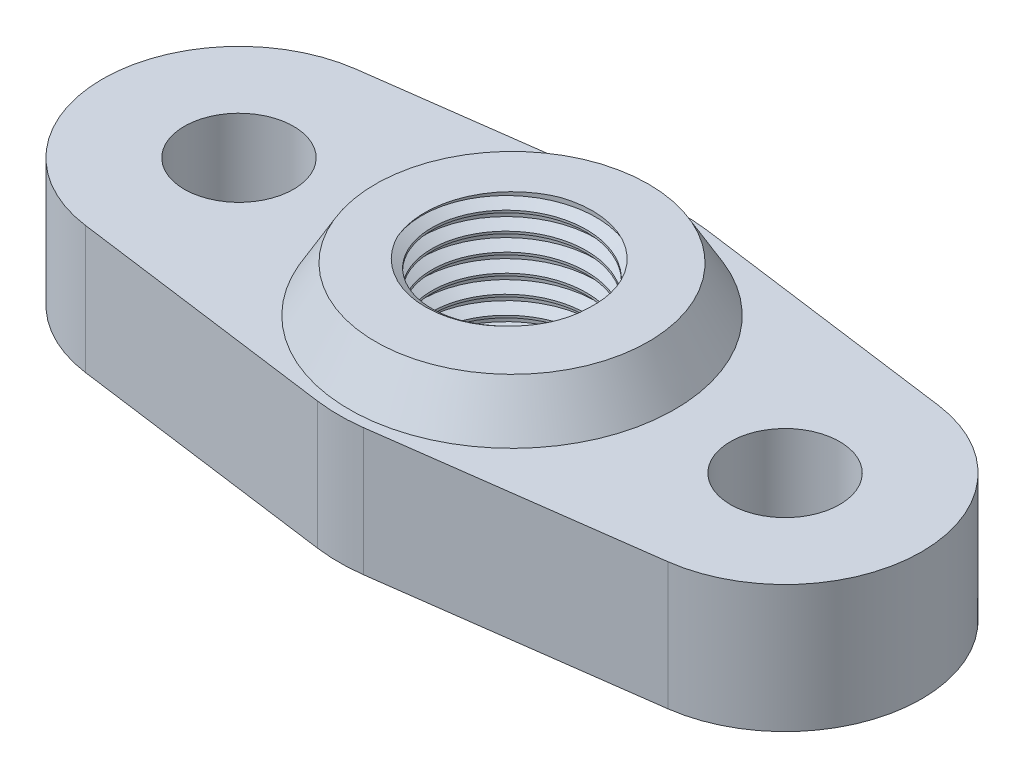
SolidWorks part; units mm, degrees
ref_plane "Front Plane" through (0, 0, 0) normal (0, 0, 1) x (1, 0, 0)
ref_plane "Top Plane" through (0, 0, 0) normal (0, 1, 0) x (1, 0, 0)
ref_plane "Right Plane" through (0, 0, 0) normal (1, 0, 0) x (0, 0, -1)
sketch "Sketch1" plane through (0, 0, 0) normal (0, 1, 0) x (1, 0, 0)
  line L0 (0, 0) -> (0, 51674.8695) construction
  line L1 (0, 0) -> (51674.8695, 0) construction
  line L2 (-64, 29.7321) -> (-5.0667, 37.6607)
  line L3 (-64, -29.7321) -> (-5.0667, -37.6607)
  line L4 (64, 29.7321) -> (5.0667, 37.6607)
  line L5 (64, -29.7321) -> (5.0667, -37.6607)
  arc A0 (-64, 29.7321) -> (-64, -29.7321) centre (-60, 0) ccw
  arc A1 (-5.0667, -37.6607) -> (5.0667, -37.6607) centre (0, 0) ccw
  arc A2 (64, 29.7321) -> (64, -29.7321) centre (60, 0) cw
  arc A3 (5.0667, 37.6607) -> (-5.0667, 37.6607) centre (0, 0) ccw
  point P14 (-90, 0)
  dimension "D1" = 30
  dimension "D2" = 76
  dimension "D3" = 180
extrude "Boss-Extrude1" add sketch "Sketch1" along normal blind 28
sketch "Sketch2" plane through (0, 0, 0) normal (0, 0, 1) x (1, 0, 0)
  line L0 (0, 0) -> (0, 38) construction
  line L1 (0, 38) -> (-30, 38)
  line L2 (-30, 38) -> (-35.7735, 28)
  line L3 (-64, 28) -> (-5.0667, 28) construction
  line L4 (-30, 28) -> (-30, 49.114) construction
  line L5 (-35.7735, 28) -> (0, 28)
  line L6 (0, 28) -> (0, 38)
  dimension "D1" = 38
  dimension "D2" = 60
  dimension "D3" = 30
revolve "Revolve1" add sketch "Sketch2" angle 360 about L0
sketch "Sketch3" plane through (0, 28, 0) normal (0, 1, 0) x (1, 0, 0)
  circle A0 centre (-60, 0) radius 12
  circle A1 centre (60, 0) radius 12
  arc A3 (-64, 29.7321) -> (-64, -29.7321) centre (-60, 0) ccw construction
  arc A4 (64, -29.7321) -> (64, 29.7321) centre (60, 0) ccw construction
  dimension "D1" = 24
extrude "Cut-Extrude1" cut sketch "Sketch3" against normal up to next
sketch "Sketch6" plane through (0, 38, 0) normal (0, 1, 0) x (1, 0, 0)
  point P0 (0, 0)
hole_wizard "Ø25.0mm Dowel Hole1" positions "Sketch6" profile "Sketch5" hole size "Ø25.0" standard "ANSI Metric" end condition up to next
sketch "Sketch5" plane through (0, 38, 0) normal (1, 0, 0) x (0, 0, 1)
  line L0 (0, 0) -> (0, 38)
  line L1 (0, 38) -> (17, 38)
  line L2 (17, 38) -> (17, 0)
  line L5 (17, 0) -> (0, 0)
  line L11 (0, -6.35) -> (0, 107.95) construction
  dimension "Thru Hole Dia." = 34
  dimension "Thru Hole Depth" = 38
thread "Thread1" pitch 4 method cut profile "Thread Profile1" start angle 0, offset 6, length 48, pitch 4, diameter 34
ref_plane "Plane1" through (-17, 44, 0) normal (0, 0, -1) x (1, 0, 0)
sketch "Thread Profile1" plane through (-17, 44, 0) normal (0, 0, -1) x (1, 0, 0)
  line L0 (0, 0) -> (0, 4) construction
  line L11 (0, 0) -> (0, 3.5)
  line L12 (0, 3.5) -> (-2.1651, 2.25)
  line L13 (-2.1651, 2.25) -> (-2.1651, 1.25)
  line L15 (-2.1651, 1.25) -> (0, 0)
  line L17 (-2.1651, 1.75) -> (0, 1.75) construction
  point P2 (0, 0)
  dimension "Pitch" = 4
  dimension "Profile_Angle" = 60
  dimension "Profile_Land" = 1
  dimension "Profile_Height" = 2.1651
